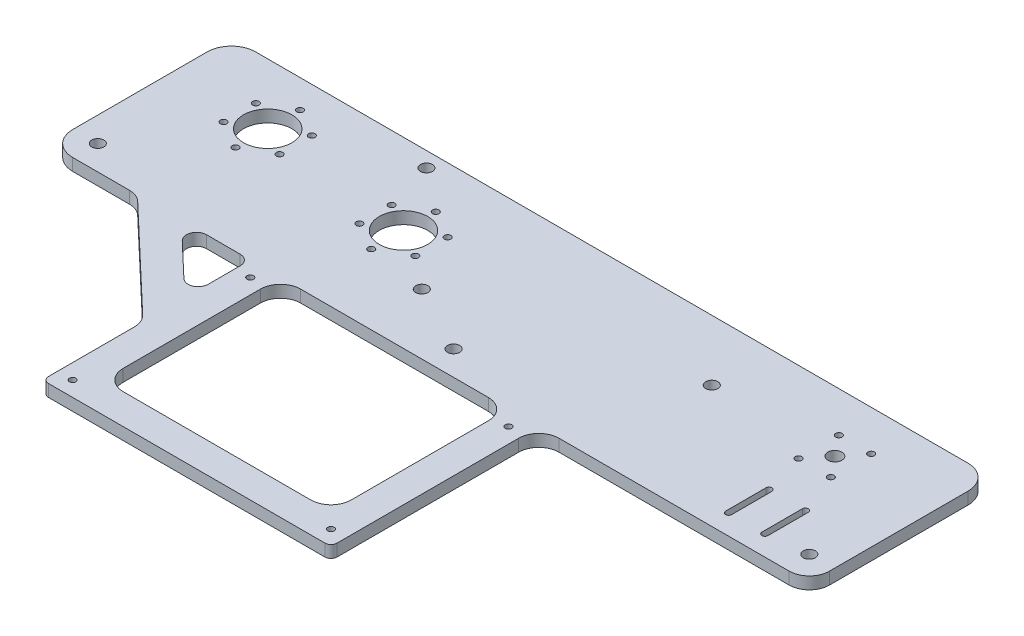
SolidWorks part; units mm, degrees
material "Policarbonato"
ref_plane "Plano frontal" through (0, 0, 0) normal (0, 0, 1) x (1, 0, 0)
ref_plane "Plano superior" through (0, 0, 0) normal (0, 1, 0) x (1, 0, 0)
ref_plane "Plano direito" through (0, 0, 0) normal (1, 0, 0) x (0, 0, -1)
sketch "Esboço1" plane through (0, 0, 0) normal (0, 1, 0) x (1, 0, 0)
  line L3 (-85.5279, -153.6487) -> (51.4721, -153.6487)
  line L4 (54.4721, -150.6487) -> (54.4721, -108.1025)
  line L6 (188.5279, -40.6487) -> (188.5279, 28)
  line L7 (176.5279, 40) -> (-176.5279, 40)
  line L8 (-188.5279, 28) -> (-188.5279, -38.6487)
  line L9 (-176.5279, -50.6487) -> (-148.4656, -50.6487)
  line L10 (-141.5771, -53.3996) -> (-91.6394, -100.8535)
  line L11 (-88.5279, -108.1025) -> (-88.5279, -150.6487)
  line L12 (-110.1764, -50.6487) -> (-93.5279, -50.6487)
  line L13 (-88.5279, -55.6487) -> (-88.5279, -71.4691)
  line L14 (-96.9722, -75.0936) -> (-113.6207, -59.2732)
  line L15 (39.4721, -60.6487) -> (39.4721, -128.6487)
  line L16 (29.4721, -138.6487) -> (-63.5279, -138.6487)
  line L17 (-73.5279, -128.6487) -> (-73.5279, -60.6487)
  line L18 (-63.5279, -50.6487) -> (29.4721, -50.6487)
  line L20 (132.5279, 0) -> (148.5279, 0) construction
  line L21 (132.5279, 0) -> (132.5279, 20) construction
  line L22 (132.5279, 20) -> (148.5279, 20) construction
  line L23 (148.5279, 0) -> (148.5279, 20) construction
  line L24 (132.5279, 0) -> (148.5279, 20) construction
  line L25 (132.5279, 20) -> (148.5279, 0) construction
  line L29 (54.4721, -108.1025) -> (54.4721, -60.6487)
  line L30 (64.4721, -50.6487) -> (178.5279, -50.6487)
  line L31 (156.5279, -40.6487) -> (156.5279, -20.6487) construction
  line L32 (155.0279, -40.6487) -> (155.0279, -20.6487)
  line L33 (158.0279, -40.6487) -> (158.0279, -20.6487)
  line L34 (147.5279, -45.2211) -> (147.5279, -21.4375) construction
  line L36 (138.5279, -40.6487) -> (138.5279, -20.6487) construction
  line L37 (140.0279, -40.6487) -> (140.0279, -20.6487)
  line L38 (137.0279, -40.6487) -> (137.0279, -20.6487)
  circle A0 centre (-81.0279, -58.1487) radius 1.6
  circle A1 centre (-81.0279, -146.1487) radius 1.6
  circle A2 centre (46.9721, -58.1487) radius 1.6
  circle A3 centre (46.9721, -146.1487) radius 1.6
  circle A8 centre (176.311, -38.4318) radius 3
  circle A9 centre (0, -38.4318) radius 3
  circle A11 centre (-140.5279, 10) radius 12
  circle A20 centre (-140.5279, 10) radius 16 construction
  circle A21 centre (-140.5279, -6) radius 1.6
  circle A22 centre (-154.3843, 2) radius 1.6
  circle A23 centre (-154.3843, 18) radius 1.6
  circle A24 centre (-84.3674, 32.5) radius 3
  circle A25 centre (-176.311, -38.4318) radius 3
  circle A26 centre (140.5279, 10) radius 3.5
  circle A27 centre (148.5279, 0) radius 1.6
  circle A28 centre (148.5279, 20) radius 1.6
  circle A29 centre (132.5279, 0) radius 1.6
  circle A30 centre (132.5279, 20) radius 1.6
  arc A31 (51.4721, -153.6487) -> (54.4721, -150.6487) centre (51.4721, -150.6487) ccw
  arc A34 (188.5279, 28) -> (176.5279, 40) centre (176.5279, 28) ccw
  arc A35 (-176.5279, 40) -> (-188.5279, 28) centre (-176.5279, 28) ccw
  arc A36 (-188.5279, -38.6487) -> (-176.5279, -50.6487) centre (-176.5279, -38.6487) ccw
  arc A37 (-91.6394, -100.8535) -> (-88.5279, -108.1025) centre (-98.5279, -108.1025) cw
  arc A38 (-88.5279, -150.6487) -> (-85.5279, -153.6487) centre (-85.5279, -150.6487) ccw
  arc A39 (-93.5279, -50.6487) -> (-88.5279, -55.6487) centre (-93.5279, -55.6487) cw
  arc A40 (-88.5279, -71.4691) -> (-96.9722, -75.0936) centre (-93.5279, -71.4691) cw
  arc A41 (-113.6207, -59.2732) -> (-110.1764, -50.6487) centre (-110.1764, -55.6487) cw
  arc A42 (39.4721, -128.6487) -> (29.4721, -138.6487) centre (29.4721, -128.6487) cw
  arc A43 (-63.5279, -138.6487) -> (-73.5279, -128.6487) centre (-63.5279, -128.6487) cw
  arc A44 (-73.5279, -60.6487) -> (-63.5279, -50.6487) centre (-63.5279, -60.6487) cw
  arc A45 (29.4721, -50.6487) -> (39.4721, -60.6487) centre (29.4721, -60.6487) cw
  circle A46 centre (-140.5279, 26) radius 1.6
  circle A47 centre (-126.6715, 18) radius 1.6
  circle A48 centre (-126.6715, 2) radius 1.6
  circle A49 centre (-63.2404, 0) radius 16 construction
  circle A50 centre (-63.2404, -16) radius 1.6
  circle A51 centre (-77.0968, -8) radius 1.6
  circle A52 centre (-77.0968, 8) radius 1.6
  circle A53 centre (-63.2404, 16) radius 1.6
  circle A54 centre (-49.384, 8) radius 1.6
  circle A55 centre (-49.384, -8) radius 1.6
  circle A56 centre (-63.2404, 0) radius 12
  circle A57 centre (-33.5279, -20.6487) radius 3
  circle A58 centre (79.5279, 10) radius 3
  arc A61 (-148.4656, -50.6487) -> (-141.5771, -53.3996) centre (-148.4656, -60.6487) cw
  arc A62 (188.5279, -40.6487) -> (178.5279, -50.6487) centre (178.5279, -40.6487) cw
  arc A63 (54.4721, -60.6487) -> (64.4721, -50.6487) centre (64.4721, -60.6487) cw
  arc A64 (155.0279, -40.6487) -> (158.0279, -40.6487) centre (156.5279, -40.6487) ccw
  arc A65 (158.0279, -20.6487) -> (155.0279, -20.6487) centre (156.5279, -20.6487) ccw
  arc A66 (140.0279, -40.6487) -> (137.0279, -40.6487) centre (138.5279, -40.6487) cw
  arc A67 (137.0279, -20.6487) -> (140.0279, -20.6487) centre (138.5279, -20.6487) cw
  point P14 (156.5279, -30.6487)
  point P43 (-140.5279, 10)
  point P70 (-144.4721, -50.6487)
  point P116 (-63.2404, 0)
  point P123 (0, 40)
  point P124 (138.5279, -30.6487)
  dimension "D2" = 3
  dimension "D7" = 10
  dimension "D8" = 12
  dimension "D10" = 90.6487
  dimension "D11" = 61
  dimension "D12" = 77.2875
  dimension "D13" = 7.5
  dimension "D14" = 104.1605
  dimension "D16" = 12
  dimension "D20" = 10
  dimension "D21" = 3
  dimension "D22" = 48.4318
  dimension "D23" = 32
  dimension "D24" = 3.2
  dimension "D25" = 6
  dimension "D26" = 24
  dimension "D27" = 48
  dimension "D28" = 30
  dimension "D29" = 40
  dimension "D30" = 6
  dimension "D34" = 30
  dimension "D31" = 32
  dimension "D32" = 3.2
  dimension "D33" = 24
  dimension "D35" = 6
  dimension "D36" = 155
  dimension "D37" = 30
  dimension "D44" = 7
  dimension "D48" = 10
  dimension "D54" = 143
  dimension "D6" = 10
  dimension "D58" = 5
  dimension "D62" = 1.5
  dimension "D1" = 137
  dimension "D3" = 42.5462
  dimension "D9" = 377.0558
  dimension "D15" = 66.6487
  dimension "D17" = 32.0558
  dimension "D18" = 100
  dimension "D19" = 42.5462
  dimension "D38" = 48
  dimension "D39" = 15
  dimension "D40" = 12.2169
  dimension "D41" = 12.2169
  dimension "D42" = 16
  dimension "D43" = 20
  dimension "D45" = 15
  dimension "D46" = 15
  dimension "D47" = 15
  dimension "D49" = 7.5
  dimension "D50" = 7.5
  dimension "D51" = 88
  dimension "D52" = 128
  dimension "D53" = 93
  dimension "D55" = 15
  dimension "D56" = 20.6487
  dimension "D57" = 68
  dimension "D59" = 32
  dimension "D60" = 10
  dimension "D61" = 20
  dimension "D63" = 9
extrude "Ressalto-extrusão1" add sketch "Esboço1" against normal blind 6
